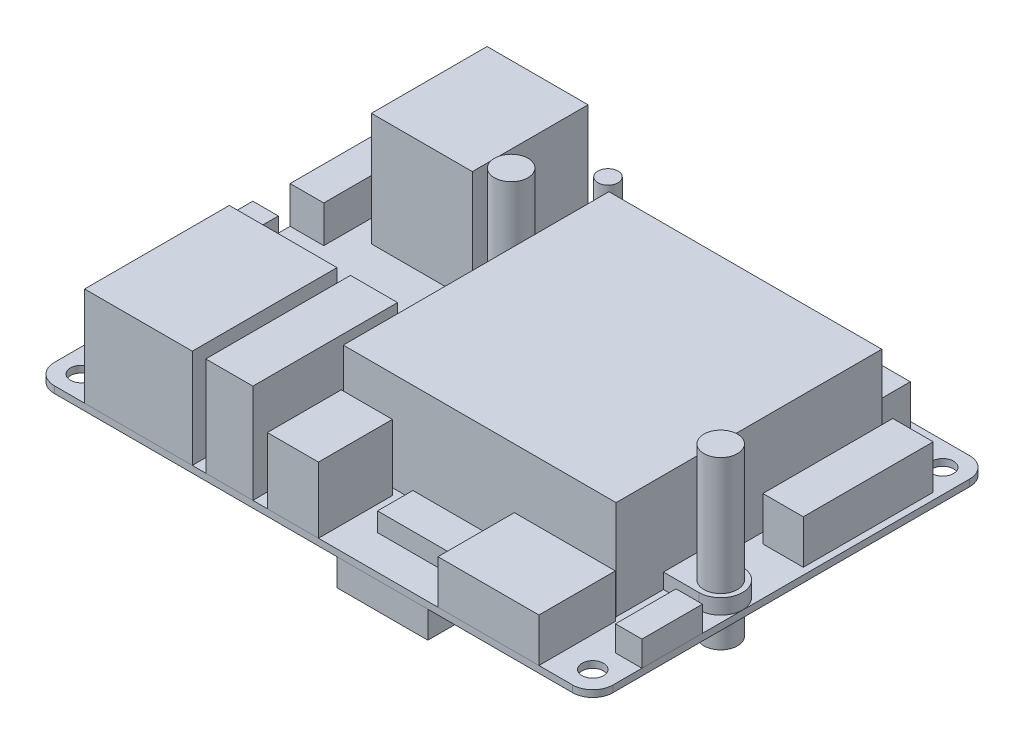
SolidWorks part; units mm, degrees
material "Silicon"
ref_plane "Front Plane" through (0, 0, 0) normal (0, 0, 1) x (1, 0, 0)
ref_plane "Top Plane" through (0, 0, 0) normal (0, 1, 0) x (1, 0, 0)
ref_plane "Right Plane" through (0, 0, 0) normal (1, 0, 0) x (0, 0, -1)
sketch "Sketch1" plane through (0, 0, 0) normal (0, 1, 0) x (1, 0, 0)
  line L1 (-38.5, -29.5) -> (38.5, -29.5)
  line L2 (-41.5, -26.5) -> (-41.5, 26.5)
  line L3 (-38.5, 29.5) -> (38.5, 29.5)
  line L4 (41.5, -26.5) -> (41.5, 26.5)
  line L5 (-41.5, -29.5) -> (41.5, 29.5) construction
  line L6 (-41.5, 29.5) -> (41.5, -29.5) construction
  arc A0 (38.5, 29.5) -> (41.5, 26.5) centre (38.5, 26.5) cw
  arc A1 (38.5, -29.5) -> (41.5, -26.5) centre (38.5, -26.5) ccw
  arc A2 (-38.5, -29.5) -> (-41.5, -26.5) centre (-38.5, -26.5) cw
  arc A3 (-41.5, 26.5) -> (-38.5, 29.5) centre (-38.5, 26.5) cw
  point P0 (0, 0)
  dimension "D3" = 3
  dimension "D1" = 83
  dimension "D2" = 59
extrude "PCB Extrude" add sketch "Sketch1" against normal blind 1
ref_plane "Plane_UnderSurface" through (0, -0.1, 0) normal (0, 1, 0) x (1, 0, 0)
ref_plane "Plane_AboveTop" through (0, 1, 0) normal (0, 1, 0) x (1, 0, 0)
sketch "IMAGE_TOP_PADS" plane through (0, 1, 0) normal (0, 1, 0) x (1, 0, 0)
  line L0 (-47.2752, 1.0682) -> (46.7248, 1.0682) construction
  line L2 (-41.5535, -29.5341) -> (41.4465, -29.5341) construction
  line L31 (-40.884, -25.1069) -> (-40.884, 27.8931) construction
  dimension "D1" = 53
  dimension "D2" = 83
sketch "IMAGE_TOP_COMPONENTS" plane through (0, 1, 0) normal (0, 1, 0) x (1, 0, 0)
  line L0 (-41.4491, -26.8822) -> (41.5509, -26.8822) construction
  dimension "D1" = 83
sketch "IMAGE_BOTTOM_COMPONENTS" plane through (0, -1, 0) normal (0, -1, 0) x (1, 0, 0)
  line L0 (-41.5726, -13.5939) -> (41.4274, -13.5939) construction
  dimension "D1" = 83
sketch "Sketch3" plane through (0, 0, 0) normal (0, 1, 0) x (1, 0, 0)
  line L0 (-38, -26) -> (38, -26) construction
  line L1 (-38, -26) -> (-38, 26) construction
  line L4 (38.5, 29.5) -> (-38.5, 29.5)
  line L5 (-41.5, 26.5) -> (-41.5, -26.5)
  line L6 (-38.5, -29.5) -> (38.5, -29.5)
  line L7 (41.5, -26.5) -> (41.5, 26.5)
  line L8 (38.5, 29.5) -> (-38.5, 29.5) construction
  line L9 (-41.5, 26.5) -> (-41.5, -26.5) construction
  line L10 (-38.5, -29.5) -> (38.5, -29.5) construction
  line L11 (41.5, -26.5) -> (41.5, 26.5) construction
  circle A0 centre (-12.8308, 12.7046) radius 1.6
  circle A1 centre (38.2313, -7.2227) radius 1.6
  circle A2 centre (-38, 26) radius 1.6
  circle A4 centre (38, 26) radius 1.6
  circle A6 centre (38, -26) radius 1.6
  arc A7 (41.5, 26.5) -> (38.5, 29.5) centre (38.5, 26.5) ccw
  circle A8 centre (-38, -26) radius 1.6
  arc A9 (-38.5, 29.5) -> (-41.5, 26.5) centre (-38.5, 26.5) ccw
  arc A10 (-41.5, -26.5) -> (-38.5, -29.5) centre (-38.5, -26.5) ccw
  arc A11 (38.5, -29.5) -> (41.5, -26.5) centre (38.5, -26.5) ccw
  arc A12 (41.5, 26.5) -> (38.5, 29.5) centre (38.5, 26.5) ccw construction
  arc A13 (-38.5, 29.5) -> (-41.5, 26.5) centre (-38.5, 26.5) ccw construction
  arc A14 (-41.5, -26.5) -> (-38.5, -29.5) centre (-38.5, -26.5) ccw construction
  arc A15 (38.5, -29.5) -> (41.5, -26.5) centre (38.5, -26.5) ccw construction
  point P0 (0, -26)
  point P6 (-38, 0)
  dimension "D1" = 3.2
  dimension "D2" = 52
  dimension "D3" = 76
  dimension "D4" = 0
extrude "PCB Holes and Tabs" cut sketch "Sketch3" against normal through all
sketch "Gross Components" plane through (-30.6818, 0, -29.2971) normal (0, 1, 0) x (1, 0, 0)
  line L0 (69.1818, 0.2029) -> (-7.8182, 0.2029) construction
  line L1 (15.4442, 0.2029) -> (21.4442, 0.2029)
  line L2 (15.4442, 0.2029) -> (15.4442, -5.7971)
  line L3 (15.4442, -5.7971) -> (21.4442, -5.7971)
  line L4 (21.4442, 0.2029) -> (21.4442, -5.7971)
  line L5 (-10.8182, -8.5628) -> (-10.8182, -20.7628)
  line L6 (-10.8182, -2.7971) -> (-10.8182, -55.7971) construction
  line L7 (-10.8182, -20.7628) -> (-5.8182, -20.7628)
  line L8 (-5.8182, -20.7628) -> (-5.8182, -9.977)
  line L9 (-5.8182, -9.977) -> (-7.2324, -8.5628)
  line L10 (-7.2324, -8.5628) -> (-10.8182, -8.5628)
  line L11 (72.1818, -55.7971) -> (72.1818, -2.7971) construction
  line L12 (-10.8182, -26.3049) -> (-7.0182, -26.3049)
  line L13 (-10.8182, -26.3049) -> (-10.8182, -33.6049)
  line L14 (-10.8182, -33.6049) -> (-7.0182, -33.6049)
  line L15 (-7.0182, -26.3049) -> (-7.0182, -33.6049)
  line L16 (19.72, -36.9097) -> (15.92, -36.9097)
  line L17 (19.72, -36.9097) -> (19.72, -29.6097)
  line L18 (19.72, -29.6097) -> (15.92, -29.6097)
  line L19 (15.92, -36.9097) -> (15.92, -29.6097)
  line L20 (35.097, -48.438) -> (46.497, -48.438)
  line L21 (35.097, -48.438) -> (35.097, -53.688)
  line L22 (35.097, -53.688) -> (46.497, -53.688)
  line L23 (46.497, -48.438) -> (46.497, -53.688)
  line L24 (72.1818, -42.4971) -> (68.2513, -42.4971)
  line L25 (72.1818, -42.4971) -> (72.1818, -51.4971)
  line L26 (72.1818, -51.4971) -> (68.2513, -51.4971)
  line L27 (68.2513, -42.4971) -> (68.2513, -51.4971)
  line L28 (68.9131, -39.7698) -> (63.6539, -39.7698)
  line L29 (23.1192, -46.8041) -> (63.6539, -46.8041)
  line L30 (23.1192, -46.8041) -> (23.1192, -7.329)
  line L31 (23.1192, -7.329) -> (63.6539, -7.329)
  line L32 (63.6539, -46.8041) -> (63.6539, -7.329)
  line L33 (23.8276, -47.8135) -> (31.4276, -47.8135)
  line L34 (23.8276, -47.8135) -> (23.8276, -58.7971)
  line L35 (23.8276, -58.7971) -> (31.4276, -58.7971)
  line L36 (31.4276, -47.8135) -> (31.4276, -58.7971)
  line L37 (68.9131, -33.2698) -> (63.6539, -33.2698)
  line L38 (17.851, -19.8425) -> (23.1192, -19.8425)
  line L39 (17.851, -13.3425) -> (23.1192, -13.3425)
  line L40 (-2.5182, 0.2029) -> (-2.5182, -16.9903)
  line L41 (-2.5182, -16.9903) -> (12.4818, -16.9903)
  line L42 (12.4818, -16.9903) -> (12.4818, 0.2029)
  line L43 (12.4818, 0.2029) -> (-2.5182, 0.2029)
  line L44 (-3.3182, -58.7971) -> (-3.3182, -37.2971)
  line L45 (-7.8182, -58.7971) -> (69.1818, -58.7971) construction
  line L46 (-3.3182, -37.2971) -> (12.6818, -37.2971)
  line L47 (12.6818, -37.2971) -> (12.6818, -58.7971)
  line L48 (12.6818, -58.7971) -> (-3.3182, -58.7971)
  line L49 (14.6818, -58.7971) -> (14.6818, -37.2971)
  line L50 (14.6818, -37.2971) -> (21.6818, -37.2971)
  line L51 (21.6818, -37.2971) -> (21.6818, -58.7971)
  line L52 (21.6818, -58.7971) -> (14.6818, -58.7971)
  line L53 (49.1818, -58.7971) -> (49.1818, -47.4469)
  line L54 (49.1818, -47.4469) -> (64.1818, -47.4469)
  line L55 (64.1818, -47.4469) -> (64.1818, -58.7971)
  line L56 (64.1818, -58.7971) -> (49.1818, -58.7971)
  line L57 (24.4567, -7.1971) -> (24.4567, -1.1971)
  line L58 (24.4567, -1.1971) -> (61.7567, -1.1971)
  line L59 (61.7567, -1.1971) -> (61.7567, -7.1971)
  line L60 (61.7567, -7.1971) -> (24.4567, -7.1971)
  line L61 (65.1818, -7.2218) -> (65.1818, -26.5218)
  line L62 (65.1818, -26.5218) -> (71.1818, -26.5218)
  line L63 (71.1818, -26.5218) -> (71.1818, -7.2218)
  line L64 (71.1818, -7.2218) -> (65.1818, -7.2218)
  arc A0 (17.851, -13.3425) -> (17.851, -19.8425) centre (17.851, -16.5925) ccw
  arc A1 (68.9131, -39.7698) -> (68.9131, -33.2698) centre (68.9131, -36.5198) ccw
  circle A2 centre (17.851, -16.5925) radius 1.6 construction
  circle A3 centre (17.851, -16.5925) radius 1.6
  circle A4 centre (68.9131, -36.5198) radius 1.6 construction
  circle A5 centre (68.9131, -36.5198) radius 1.6
  circle M1 centre (68.9131, -36.5198) radius 1.6
  circle M2 centre (17.851, -16.5925) radius 1.6
  line M10 (-10.8182, -2.7971) -> (-10.8182, -55.7971)
  line M12 (-7.8182, -58.7971) -> (69.1818, -58.7971)
  line M14 (72.1818, -55.7971) -> (72.1818, -2.7971)
  dimension "D1" = 3.25
  dimension "D2" = 3.25
  dimension "D3" = 12.2
  dimension "D4" = 5
  dimension "D5" = 7.3
  dimension "D6" = 3.8
  dimension "D7" = 15
  dimension "D8" = 7.6
  dimension "D9" = 8.3
  dimension "D10" = 6
  dimension "D11" = 6
  dimension "D12" = 16
  dimension "D13" = 21.5
  dimension "D14" = 7.5
  dimension "D15" = 2
  dimension "D16" = 7
  dimension "D17" = 21.5
  dimension "D18" = 15
  dimension "D19" = 8
  dimension "D20" = 11.4
  dimension "D21" = 5.25
  dimension "D22" = 2
  dimension "D23" = 37.3
  dimension "D24" = 1.4
  dimension "D25" = 6
  dimension "D26" = 6
  dimension "D27" = 19.3
  dimension "D28" = 7.3
  dimension "D29" = 9
  dimension "D30" = 1
  dimension "D31" = 45
extrude "UART Extrude" add sketch "Gross Components" along normal blind 5.5 contours L9 L10 L7 L8 M10 region at (-39.0338, 0, -14.5405)
extrude "Battery and Fan Header" add sketch "Sketch4<3>" along normal blind 6 contours L15 L12 L14 M10 | L19 L18 L17 L16 region at (-39.6, 0, 0.6578)
sketch "Sketch4<3>" plane through (-30.6818, 0, -29.2971) normal (0, 1, 0) x (1, 0, 0) same geometry as "Gross Components"
extrude "HeatSink_Fan" add sketch "Sketch4<4>" along normal blind 14.7 contours L29 L32 L31 L30 region at (12.7048, 0, -2.2305)
sketch "Sketch4<4>" plane through (-30.6818, 0, -29.2971) normal (0, 1, 0) x (1, 0, 0) same geometry as "Gross Components"
extrude "PowerButton" add sketch "Sketch4<6>" along normal blind 3.5 contours L3 L4 L1 L2
sketch "Sketch4<6>" plane through (-30.6818, 0, -29.2971) normal (0, 1, 0) x (1, 0, 0) same geometry as "Gross Components"
sketch "Sketch5" plane through (0, 3.5, 0) normal (0, 1, 0) x (1, 0, 0)
  line L0 (-15.2376, 29.5) -> (-9.2376, 23.5) construction
  circle A0 centre (-12.2376, 26.5) radius 1.5
  dimension "D1" = 3
extrude "PowerButtonSwitch" add sketch "Sketch5" along normal blind 8.5
extrude "DCPowerJack" add sketch "Sketch4<8>" along normal blind 9.8 contours L35 L36 L33 L34
sketch "Sketch4<8>" plane through (-30.6818, 0, -29.2971) normal (0, 1, 0) x (1, 0, 0) same geometry as "Gross Components"
extrude "HeatSinkMountTabs" add sketch "Sketch4<11>" along normal blind 2.25 contours L39 A0 L38 L30 M2 | L28 A1 L37 L32 M14 M1 region at (35.6017, 0, 10.3656) region at (-10.1967, 0, -9.5618)
sketch "Sketch4<11>" plane through (-30.6818, 0, -29.2971) normal (0, 1, 0) x (1, 0, 0) same geometry as "Gross Components"
sketch "Sketch6" plane through (0, 2.25, 0) normal (0, 1, 0) x (1, 0, 0)
  circle A0 centre (38.2313, -7.2227) radius 2.5
  circle A1 centre (-12.8308, 12.7046) radius 2.5
  dimension "D1" = 5
extrude "HeatSinkSprings" add sketch "Sketch6" along normal blind 17.5
extrude "microSD" add sketch "Sketch4<13>" along normal blind 2.8 contours L22 L23 L20 L21
sketch "Sketch4<13>" plane through (-30.6818, 0, -29.2971) normal (0, 1, 0) x (1, 0, 0) same geometry as "Gross Components"
sketch "Sketch7" plane through (0, -1, 0) normal (0, -1, 0) x (1, 0, 0)
  line L0 (17, 29.5) -> (17, 11)
  line L1 (-38.5, 29.5) -> (38.5, 29.5) construction
  line L2 (17, 11) -> (3.5, 11)
  line L3 (3.5, 11) -> (3.5, 29.5)
  line L4 (3.5, 29.5) -> (17, 29.5)
  line L5 (41.5, 26.5) -> (41.5, -26.5) construction
  circle A0 centre (-12.8308, -12.7046) radius 2.5
  circle A1 centre (38.2313, 7.2227) radius 2.5
  dimension "D4" = 5
  dimension "D1" = 18.5
  dimension "D2" = 13.5
  dimension "D3" = 24.5
extrude "UnderSide" add sketch "Sketch7" along normal blind 4
extrude "Ethernet" add sketch "Gross Components<15>" along normal blind 14.7 contours L47 L46 L44 M12 region at (-26, 0, 18.75)
sketch "Gross Components<15>" plane through (-30.6818, 0, -29.2971) normal (0, 1, 0) x (1, 0, 0) same geometry as "Gross Components"
extrude "USBx2" add sketch "Gross Components<16>" along normal blind 16.8 contours L41 L42 L43 L40
sketch "Gross Components<16>" plane through (-30.6818, 0, -29.2971) normal (0, 1, 0) x (1, 0, 0) same geometry as "Gross Components"
extrude "USBvertical" add sketch "Gross Components<17>" along normal blind 14.7 contours L51 L52 L49 L50
sketch "Gross Components<17>" plane through (-30.6818, 0, -29.2971) normal (0, 1, 0) x (1, 0, 0) same geometry as "Gross Components"
extrude "HDMI" add sketch "Gross Components<18>" along normal blind 6.5 contours L53 L54 L55 L56
sketch "Gross Components<18>" plane through (-30.6818, 0, -29.2971) normal (0, 1, 0) x (1, 0, 0) same geometry as "Gross Components"
extrude "DIP" add sketch "Gross Components<19>" along normal blind 3.75 contours L26 L27 L24 L25
sketch "Gross Components<19>" plane through (-30.6818, 0, -29.2971) normal (0, 1, 0) x (1, 0, 0) same geometry as "Gross Components"
extrude "PinHeaders" add sketch "Gross Components<21>" along normal blind 6.5 contours L60 L59 L58 L57 | L63 L64 L61 L62 region at (12.4249, 0, -25.1) region at (37.5, 0, -12.4253)
sketch "Gross Components<21>" plane through (-30.6818, 0, -29.2971) normal (0, 1, 0) x (1, 0, 0) same geometry as "Gross Components"
sketch "Sketch9" plane through (0, 0, 29.5) normal (0, 0, 1) x (1, 0, 0)
  line L0 (-72.0907, 0) -> (76.0017, 0)
  line L1 (-38.5, 0) -> (-34, 0) construction
split line "SplitLine_TopPCB"
sketch "Sketch10" plane through (0, 0, 29.5) normal (0, 0, 1) x (1, 0, 0)
  line L0 (-60.8959, -1) -> (56.8491, -1)
  line L1 (-38.5, -1) -> (3.5, -1) construction
split line "SplitLine_BottomPCB"
